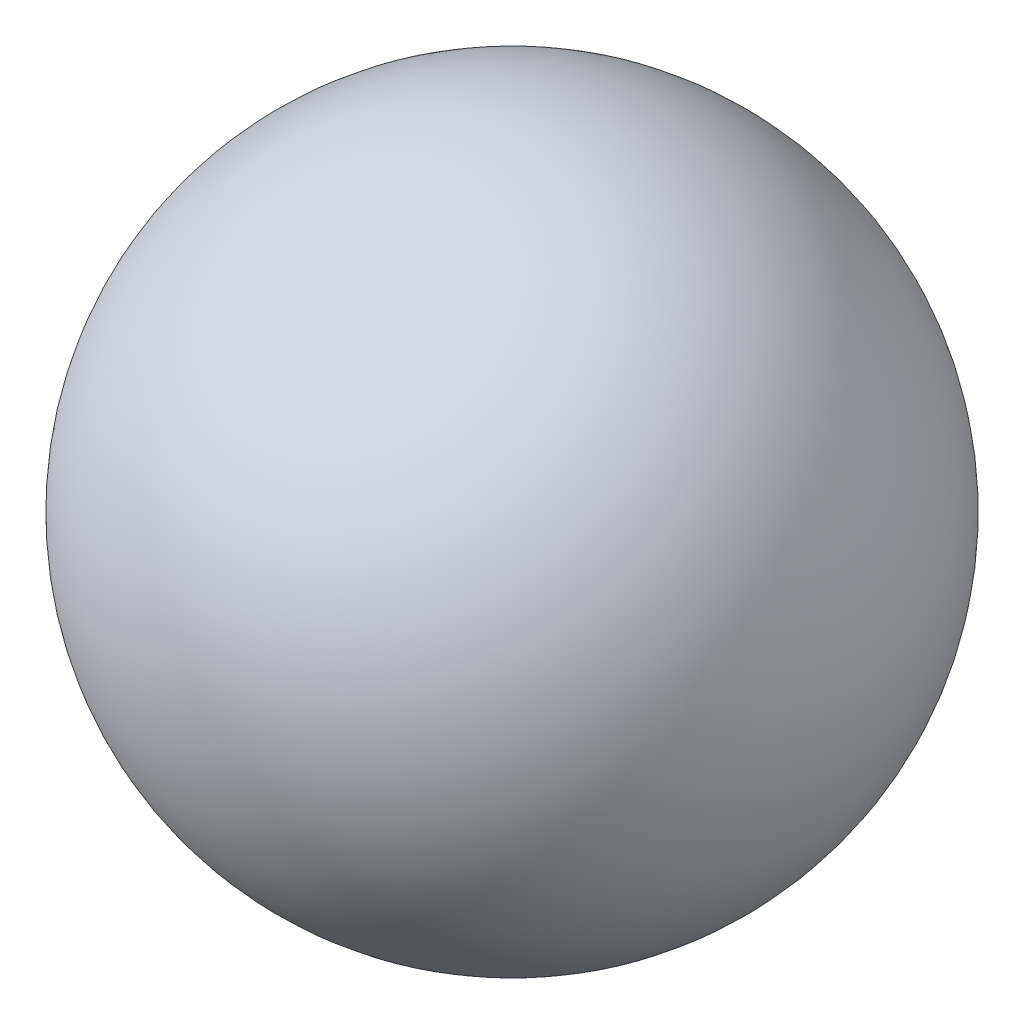
SolidWorks part; units mm, degrees
ref_plane "Front Plane" through (0, 0, 0) normal (0, 0, 1) x (1, 0, 0)
ref_plane "Top Plane" through (0, 0, 0) normal (0, 1, 0) x (1, 0, 0)
ref_plane "Right Plane" through (0, 0, 0) normal (1, 0, 0) x (0, 0, -1)
sketch "Sketch1" plane through (0, 0, 0) normal (0, 0, 1) x (1, 0, 0)
  line L0 (0, 11.5) -> (0, -11.5)
  arc A0 (0, -11.5) -> (0, 11.5) centre (0, 0) ccw
  dimension "D1" = 23
revolve "Revolve1" add sketch "Sketch1" angle 360 about L0
